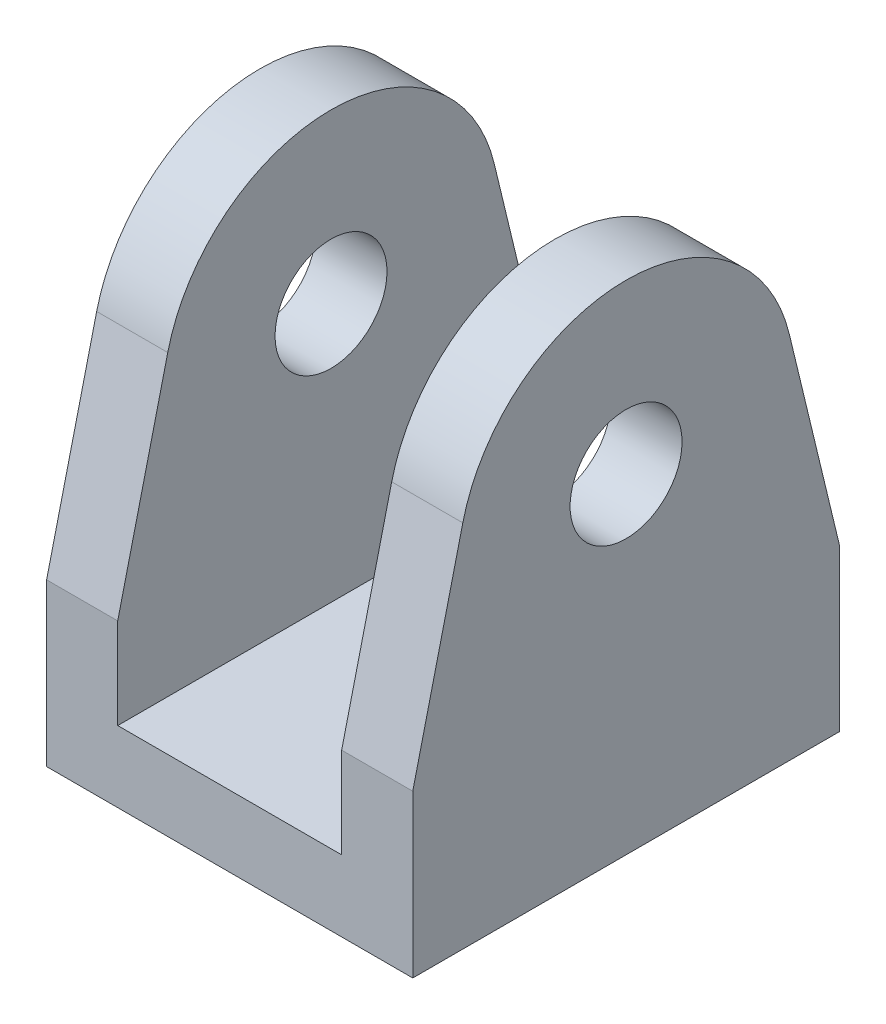
SolidWorks part; units mm, degrees
material "ABS"
ref_plane "Front Plane" through (0, 0, 0) normal (0, 0, 1) x (1, 0, 0)
ref_plane "Top Plane" through (0, 0, 0) normal (0, 1, 0) x (1, 0, 0)
ref_plane "Right Plane" through (0, 0, 0) normal (1, 0, 0) x (0, 0, -1)
sketch "Sketch1" plane through (0, 0, 0) normal (0, 1, 0) x (1, 0, 0)
  line L0 (-5, 9.525) -> (-5, -9.525)
  line L1 (-8.175, -9.525) -> (8.175, -9.525)
  line L2 (-8.175, -9.525) -> (-8.175, 9.525)
  line L3 (-8.175, 9.525) -> (8.175, 9.525)
  line L4 (8.175, -9.525) -> (8.175, 9.525)
  line L5 (-8.175, -9.525) -> (8.175, 9.525) construction
  line L6 (-8.175, 9.525) -> (8.175, -9.525) construction
  line L7 (5, 9.525) -> (5, -9.525)
  line L8 (-8.175, 0) -> (-5, 0) construction
  line L9 (5, 0) -> (8.175, 0) construction
  point P0 (0, 0)
  dimension "D1" = 19.05
  dimension "D2" = 3.175
  dimension "D3" = 10
extrude "Boss-Extrude1" add sketch "Sketch1" along normal blind 3.175 contours L3 L2 L1 L0 | L7 L3 L0 L1 | L3 L7 L1 L4 region at (0, 0, 0) region at (-6.5875, 0, 0) region at (6.5875, 0, 0)
extrude "Boss-Extrude2" add sketch "Sketch1<3>" along normal blind 19.05 from surface contours L3 L2 L1 L0 | L3 L7 L1 L4 region at (-6.5875, 0, 0) region at (6.5875, 0, 0) starting at face at (0, 3.175, 0)
sketch "Sketch1<3>" plane through (0, 0, 0) normal (0, 1, 0) x (1, 0, 0) same geometry as "Sketch1"
sketch "Sketch2" plane through (8.175, 0, 0) normal (1, 0, 0) x (0, 0, -1)
  line L0 (9.525, 22.225) -> (-9.525, 22.225) construction
  line L1 (-9.525, 7.225) -> (-7.2907, 16.4843)
  line L2 (-9.525, 22.225) -> (-9.525, 0) construction
  line L3 (9.525, 7.225) -> (7.2907, 16.4843)
  line L4 (9.525, 22.225) -> (9.525, 0) construction
  line L5 (-9.525, 7.225) -> (9.525, 7.225) construction
  line L6 (-9.525, 7.225) -> (-9.525, 22.225)
  line L7 (-9.525, 22.225) -> (0, 22.225)
  line L8 (0, 22.225) -> (9.525, 22.225)
  line L9 (9.525, 22.225) -> (9.525, 7.225)
  arc A0 (7.2907, 16.4843) -> (-7.2907, 16.4843) centre (0, 14.725) ccw
  arc A1 (-7.2907, 16.4843) -> (0, 7.225) centre (0, 14.725) ccw construction
  arc A2 (0, 7.225) -> (7.2907, 16.4843) centre (0, 14.725) ccw construction
  line M2 (9.525, 0) -> (9.525, 22.225)
  line M3 (9.525, 22.225) -> (-9.525, 22.225)
  line M4 (-9.525, 22.225) -> (-9.525, 0)
  dimension "D1" = 15
extrude "Cut-Extrude1" cut sketch "Sketch2" against normal through all contours A0 L1 M3 M4 | A0 L3 M2 M3 region at (8.175, 17.9753, 7.6415) region at (8.175, 17.9753, -7.6415)
hole_wizard "Ø5.0mm Dowel Hole1" positions "Sketch3" profile "Sketch4" hole size "Ø5.0" standard "ANSI Metric" end condition through all
sketch "Sketch3" plane through (8.175, 0, 0) normal (1, 0, 0) x (0, 0, -1)
  arc A0 (7.2907, 16.4843) -> (-7.2907, 16.4843) centre (0, 14.725) ccw construction
  point P0 (0, 14.725)
sketch "Sketch4" plane through (8.175, 14.725, 0) normal (0, 1, 0) x (0, 0, -1)
  line L0 (0, 0) -> (0, 16.35)
  line L1 (0, 16.35) -> (2.5, 16.35)
  line L2 (2.5, 16.35) -> (2.5, 0)
  line L5 (2.5, 0) -> (0, 0)
  line L11 (0, -6.35) -> (0, 107.95) construction
  dimension "Thru Hole Dia." = 5
  dimension "Thru Hole Depth" = 16.35
